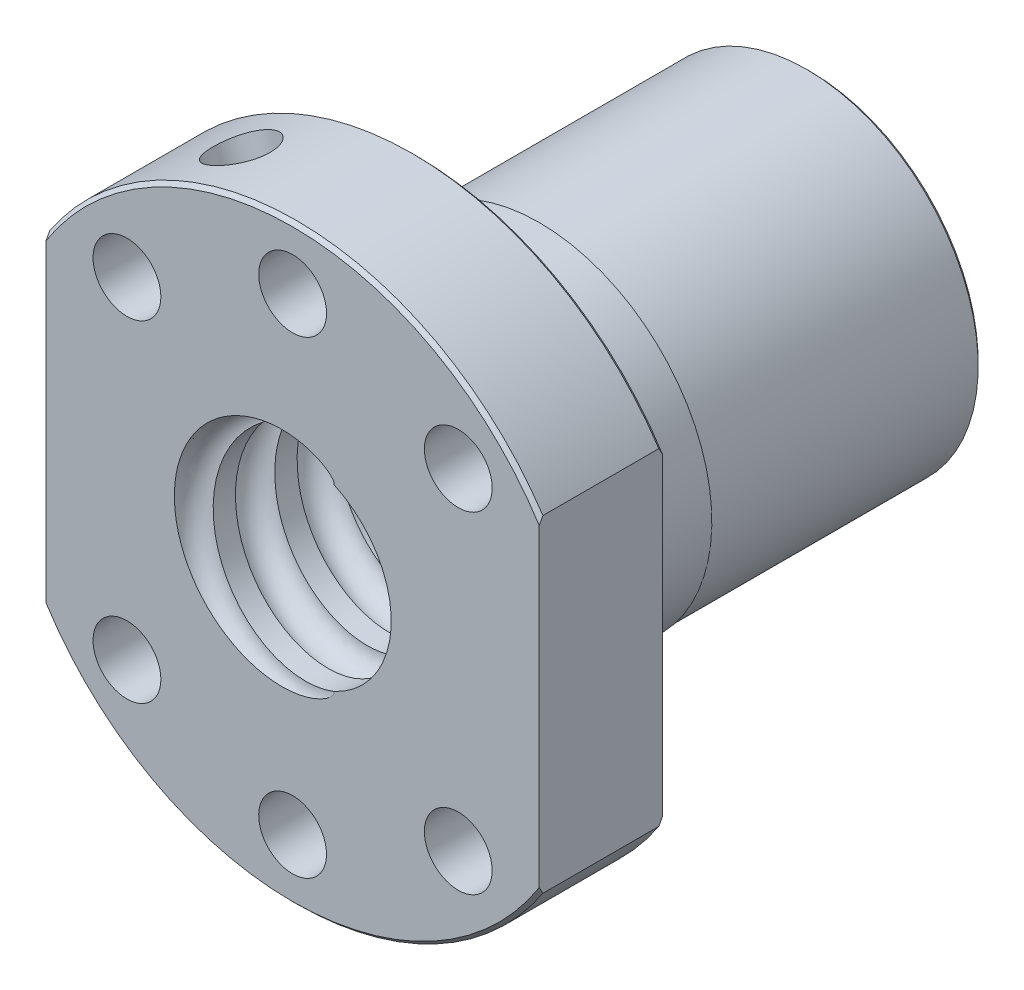
SolidWorks part; units mm, degrees
ref_plane "Front Plane" through (0, 0, 0) normal (0, 0, 1) x (1, 0, 0)
ref_plane "Top Plane" through (0, 0, 0) normal (0, 1, 0) x (1, 0, 0)
ref_plane "Right Plane" through (0, 0, 0) normal (1, 0, 0) x (0, 0, -1)
sketch "Sketch1" plane through (0, 0, 0) normal (1, 0, 0) x (0, 0, -1)
  line L0 (0, 0) -> (0, 24)
  line L1 (0, 24) -> (10, 24)
  line L2 (10, 24) -> (10, 14)
  line L3 (10, 14) -> (20, 14)
  line L4 (42, 13.9) -> (42, 0)
  line L5 (42, 0) -> (0, 0)
  line L6 (20, 14) -> (20, 13.9)
  line L7 (20, 13.9) -> (42, 13.9)
  dimension "D1" = 24
  dimension "D2" = 10
  dimension "D3" = 42
  dimension "D4" = 14
  dimension "D5" = 13.9
  dimension "D6" = 10
revolve "Revolve1" add sketch "Sketch1" angle 360 about L5
sketch "Sketch2" plane through (0, 0, 0) normal (0, 0, 1) x (1, 0, 0)
  line L0 (-20, 13.2665) -> (-20, -13.2665)
  line L1 (-20, -13.2665) -> (-34, -13.2665)
  line L2 (-34, -13.2665) -> (-34, 13.2665)
  line L3 (-34, 13.2665) -> (-20, 13.2665)
  line L4 (0, 0) -> (0, 24) construction
  line L5 (34, 13.2665) -> (20, 13.2665)
  line L6 (34, -13.2665) -> (34, 13.2665)
  line L7 (20, -13.2665) -> (34, -13.2665)
  line L8 (20, 13.2665) -> (20, -13.2665)
  circle A0 centre (0, 0) radius 24 construction
  dimension "D1" = 20
  dimension "D2" = 10
extrude "Cut-Extrude1" cut sketch "Sketch2" against normal blind 10
hole_wizard "Ø25.0 (25) Diameter Hole1" positions "Sketch3" profile "Sketch5" hole size "Ø25.0" standard "ISO" end condition through all
sketch "Sketch3" plane through (0, 0, -42) normal (0, 0, -1) x (-1, 0, 0)
  point P0 (0, 0)
sketch "Sketch5" plane through (0, 0, -42) normal (1, 0, 0) x (0, 1, 0)
  line L0 (0, 0) -> (0, 42)
  line L1 (0, 42) -> (8, 42)
  line L2 (8, 42) -> (8, 0)
  line L5 (8, 0) -> (0, 0)
  line L11 (0, -6.35) -> (0, 107.95) construction
  dimension "Thru Hole Dia." = 16
  dimension "Thru Hole Depth" = 42
hole_wizard "Ø6.6 (6.6) Diameter Hole1" positions "Sketch6" profile "Sketch7" hole size "Ø6.6" standard "ISO" end condition through all
sketch "Sketch6" plane through (0, 0, 0) normal (0, 0, 1) x (1, 0, 0)
  point P0 (0, 19)
  dimension "D1" = 19
sketch "Sketch7" plane through (0, 19, 0) normal (1, 0, 0) x (0, -1, 0)
  line L0 (0, 0) -> (0, 42)
  line L1 (0, 42) -> (2.75, 42)
  line L2 (2.75, 42) -> (2.75, 0)
  line L5 (2.75, 0) -> (0, 0)
  line L11 (0, -6.35) -> (0, 107.95) construction
  dimension "Thru Hole Dia." = 5.5
  dimension "Thru Hole Depth" = 42
pattern_circular "CirPattern1" count 8 over 360 about axis through (0, 0, 0) along (0, 0, 1) of "Ø6.6 (6.6) Diameter Hole1"
sketch "Sketch8" plane through (0, 0, 0) normal (0, 1, 0) x (1, 0, 0)
  line L0 (0, 0) -> (0, 91.9675)
ref_plane "Plane1" through (0, 0, 0) normal (-0.3827, 0.9239, 0) x (0, 0, -1)
hole_wizard "M6 Tapped Hole1" positions "Sketch9" profile "Sketch11" tap size "M6" standard "ISO" end condition through all
sketch "Sketch9" plane through (0, 0, 0) normal (-0.3827, 0.9239, 0) x (0, 0, -1)
  line L0 (10, 13.4007) -> (0, 13.4007) construction
  point P0 (5, 0)
  point P6 (5, 13.4007)
sketch "Sketch11" plane through (0, 0, -5) normal (0, 0, 1) x (0.9239, 0.3827, 0)
  line L0 (0, 0) -> (0, 29.8268)
  line L1 (0, 29.8268) -> (2.5, 29.8268)
  line L2 (2.5, 29.8268) -> (2.5, 0)
  line L5 (2.5, 0) -> (0, 0)
  line L11 (0, -6.35) -> (0, 107.95) construction
  dimension "Thru Tap Drill Dia." = 5
  dimension "Thru Tap Drill Depth" = 29.8268
cosmetic thread "Hole Thread1" parameters "D2"=6
ref_plane "Plane3" through (0, 0, 5) normal (0, 0, 1) x (1, 0, 0)
sketch "Sketch12" plane through (0, 0, 5) normal (0, 0, 1) x (1, 0, 0)
  circle A0 centre (0, 0) radius 8 construction
  circle A1 centre (0, 0) radius 8
curve "Helix/Spiral1" pitch 5 height 52.5 turns 10.5
ref_plane "Plane2" through (8, 0, -47.5) normal (0, -0.9951, -0.099) x (1, 0, 0)
sketch "Sketch13" plane through (8, 0, -47.5) normal (0, -0.9951, -0.099) x (1, 0, 0)
  circle A0 centre (0, 0) radius 1.5875
  dimension "D1" = 3.175
sweep "Cut-Sweep1" cut profiles "Sketch13" path "Helix/Spiral1" align with end faces yes
chamfer "Chamfer1" distance 0.3 angle 45 5 edges at (0, 13.9, -42) (0, -24, -10) (0, 24, -10) (0, 24, 0) (0, -24, 0)
